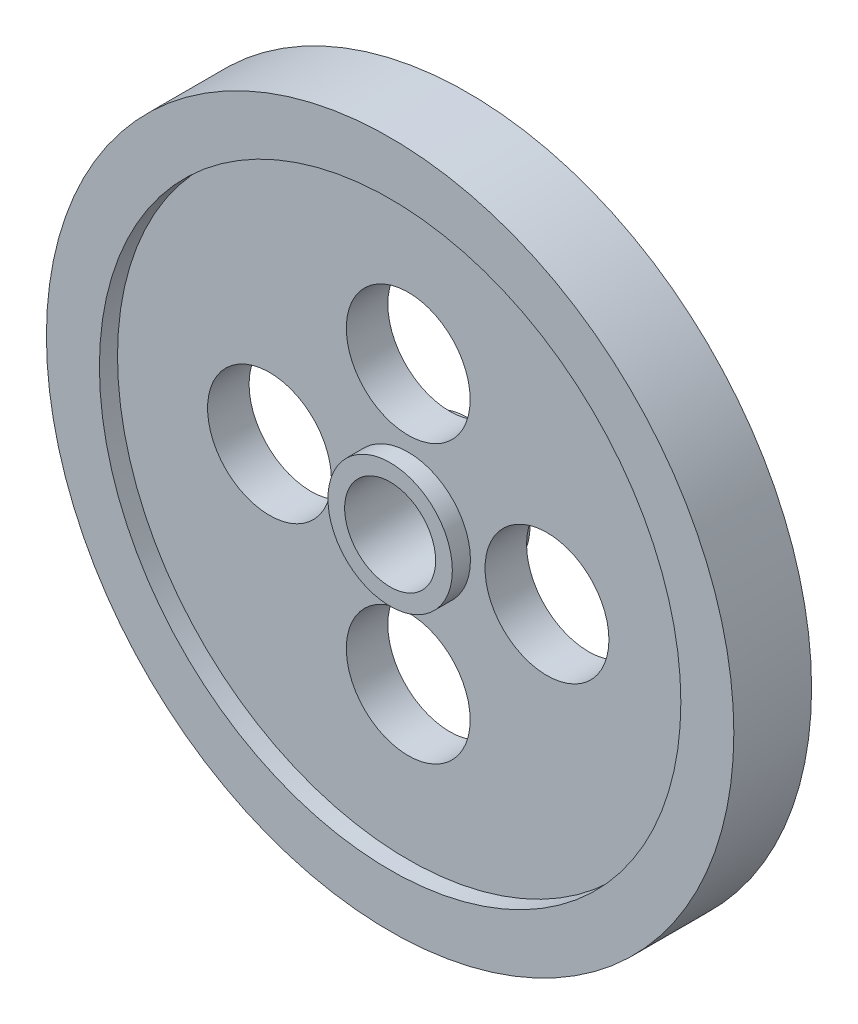
SolidWorks part; units mm, degrees
ref_plane "Front Plane" through (0, 0, 0) normal (0, 0, 1) x (1, 0, 0)
ref_plane "Top Plane" through (0, 0, 0) normal (0, 1, 0) x (1, 0, 0)
ref_plane "Right Plane" through (0, 0, 0) normal (1, 0, 0) x (0, 0, -1)
sketch "Sketch1" plane through (0, 0, 0) normal (0, 0, 1) x (1, 0, 0)
  circle A0 centre (0, 0) radius 24.6683
  circle A1 centre (0, 0) radius 3.2639
  dimension "D1" = 49.3365
  dimension "D2" = 6.5278
extrude "Boss-Extrude1" add sketch "Sketch1" along normal mid plane 5.58
sketch "Sketch2" plane through (0, 0, 2.79) normal (0, 0, 1) x (1, 0, 0)
  circle A0 centre (0, 0) radius 20.865
  circle A1 centre (0, 0) radius 4.465
  dimension "D1" = 41.73
  dimension "D2" = 8.93
extrude "Cut-Extrude1" cut sketch "Sketch2" against normal blind 1.3
sketch "Sketch3" plane through (0, 0, 1.49) normal (0, 0, 1) x (1, 0, 0)
  circle A0 centre (0, 9.9568) radius 4.445
  circle A1 centre (9.9568, 0) radius 4.445
  circle A3 centre (0, -9.9568) radius 4.445
  circle A4 centre (-9.9568, 0) radius 4.445
  point P13 (0, 0)
  dimension "D1" = 28.8036
  dimension "D2" = 8.89
  dimension "D3" = 4
extrude "Cut-Extrude2" cut sketch "Sketch3" against normal through all
mirror "Mirror1" about plane through (0, 0, 0) normal (0, 0, 1) of "Cut-Extrude1"
